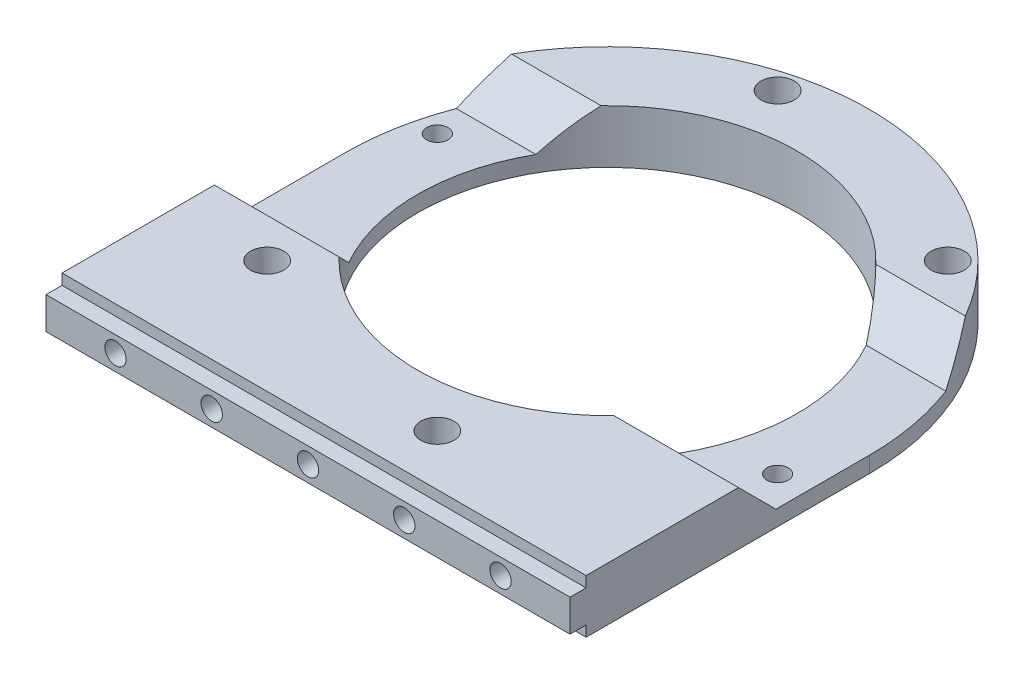
SolidWorks part; units mm, degrees
material "6061 합금"
ref_plane "정면" through (0, 0, 0) normal (0, 0, 1) x (1, 0, 0)
ref_plane "윗면" through (0, 0, 0) normal (0, 1, 0) x (1, 0, 0)
ref_plane "우측면" through (0, 0, 0) normal (1, 0, 0) x (0, 0, -1)
sketch "스케치1" plane through (0, 0, 0) normal (0, 1, 0) x (1, 0, 0)
  line L0 (-49, 0) -> (-49, -53)
  line L3 (-49, -53) -> (49, -53)
  line L4 (49, -53) -> (49, 0)
  line L5 (-43.4667, 11.6469) -> (0, 0) construction
  line L6 (0, 0) -> (-45, 0) construction
  circle A0 centre (0, 0) radius 35.5
  arc A4 (49, 0) -> (-49, 0) centre (0, 0) ccw
  circle A5 centre (0, 0) radius 45
  circle A6 centre (-43.4667, 11.6469) radius 2
  circle A7 centre (-11.6469, 43.4667) radius 2
  circle A8 centre (31.8198, 31.8198) radius 2
  circle A9 centre (43.4667, -11.6469) radius 2
  circle A10 centre (11.6469, -43.4667) radius 2
  circle A11 centre (-31.8198, -31.8198) radius 2
  point P23 (0, 0)
  dimension "D1" = 71
  dimension "D2" = 98
  dimension "D4" = 90
  dimension "D5" = 4
  dimension "D3" = 53
  dimension "D6" = 15
  dimension "D7" = 6
extrude "보스-돌출4" add sketch "스케치1" along normal blind 10 contours L4 A4 L0 L3 A11 A5 A6 A7 A8 A9 A10 | A11 A5 A10 A9 A8 A7 A6 A0 region at (0, 0, -47.5855) region at (43.4692, 0, 4.7427)
sketch "스케치24" plane through (0, 0, 53) normal (0, 0, 1) x (1, 0, 0)
  line L0 (49, 10) -> (49, 0) construction
  line L1 (-49, 2) -> (49, 2)
  line L2 (-49, 2) -> (-49, 8)
  line L3 (-49, 8) -> (49, 8)
  line L4 (49, 2) -> (49, 8)
  line L5 (-49, 2) -> (49, 8) construction
  line L6 (-49, 8) -> (49, 2) construction
  line L7 (-49, 10) -> (-49, 0) construction
  point P0 (0, 5)
  point P7 (0, 0)
  point P8 (49, 5)
  point P9 (0, 0)
  dimension "D1" = 6
extrude "보스-돌출5" add sketch "스케치24" along normal blind 3
sketch "스케치26" plane through (0, 10, 0) normal (0, 1, 0) x (1, 0, 0)
  line L1 (-49, -17.5) -> (49, -17.5)
  line L2 (-49, -17.5) -> (-49, 17.5)
  line L3 (-49, 17.5) -> (49, 17.5)
  line L4 (49, -17.5) -> (49, 17.5)
  line L5 (-49, -17.5) -> (49, 17.5) construction
  line L6 (-49, 17.5) -> (49, -17.5) construction
  line L7 (-49, 0) -> (-49, -53) construction
  point P0 (0, 0)
  point P5 (0, 0)
  point P9 (0, 0)
  point P11 (0, 0)
  point P12 (0, 0)
  point P13 (0, 0)
  point P14 (0, 0)
  dimension "D1" = 35
extrude "컷-돌출17" cut sketch "스케치26" against normal blind 7
chamfer "모따기1" distance 7 angle 45 4 edges at (-39.9434, 10, 17.5) (-38.3277, 10, -17.5) (39.9434, 10, 17.5) (38.3277, 10, -17.5)
sketch "스케치27" plane through (0, 10, 0) normal (0, 1, 0) x (1, 0, 0)
  line L0 (-11.6469, 43.4667) -> (0, 0) construction
  line L1 (0, 0) -> (31.8198, 31.8198) construction
  circle A0 centre (-11.6469, 43.4667) radius 3.1
  circle A1 centre (31.8198, 31.8198) radius 3.1
  circle A2 centre (43.4667, -11.6469) radius 3.1
  circle A3 centre (11.6469, -43.4667) radius 3.1
  circle A4 centre (-31.8198, -31.8198) radius 3.1
  circle A5 centre (-43.4667, 11.6469) radius 3.1
  point P15 (0, 0)
  dimension "D1" = 6.2
  dimension "D3" = 60
  dimension "D2" = 6
extrude "컷-돌출18" cut sketch "스케치27" against normal blind 5
sketch "스케치28" plane through (0, 0, 56) normal (0, 0, 1) x (1, 0, 0)
  line L0 (-36, 5) -> (36, 5) construction
  line L1 (0, 10) -> (0, 0) construction
  line L2 (-49, 10) -> (49, 10) construction
  line L3 (-36, 5) -> (-18, 5) construction
  circle A0 centre (-36, 5) radius 2
  circle A1 centre (-18, 5) radius 2
  circle A2 centre (0, 5) radius 2
  circle A3 centre (18, 5) radius 2
  circle A4 centre (36, 5) radius 2
  point P2 (0, 5)
  point P7 (0, 5)
  dimension "D1" = 36
  dimension "D2" = 4
  dimension "D4" = 18
  dimension "D3" = 5
extrude "컷-돌출19" cut sketch "스케치28" against normal blind 15
sketch "스케치25" plane through (0, 0, 0) normal (0, 0, 1) x (1, 0, 0)
  line L0 (-45, 10) -> (45, 10)
  line L1 (-49, 0) -> (49, 0) construction
  line L2 (-44.2719, 0) -> (-49, 0)
  line L3 (-49, 0) -> (-49, 10)
  line L5 (-49, 10) -> (-45, 10)
  line L6 (45, 10) -> (49, 10)
  line L7 (49, 10) -> (49, 0)
  line L8 (49, 0) -> (44.2719, 0)
  circle A0 centre (0, -21) radius 49
  point P4 (0, 10)
  point P10 (0, 0)
  point P15 (46.0077, -4.1391)
  point P16 (49, 14.2294)
  dimension "D1" = 98
  dimension "D2" = 90
  dimension "D3" = 31
  dimension "D4" = 10
